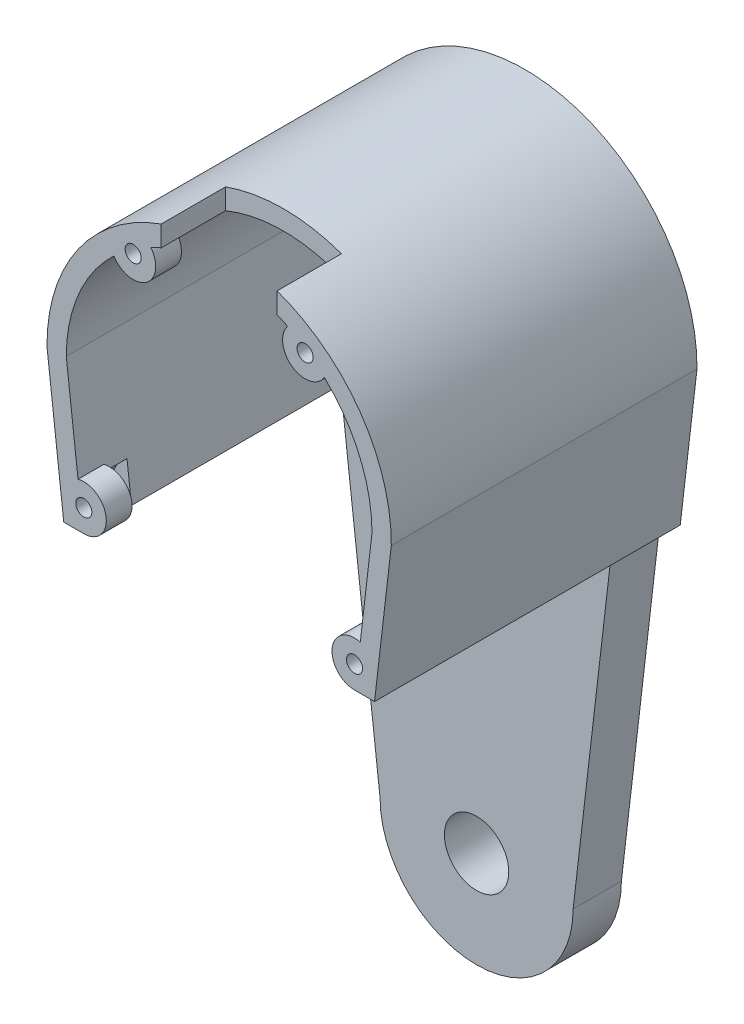
SolidWorks part; units mm, degrees
material "PLA"
ref_plane "Front" through (0, 0, 0) normal (0, 0, 1) x (1, 0, 0)
ref_plane "Top" through (0, 0, 0) normal (0, 1, 0) x (1, 0, 0)
ref_plane "Right" through (0, 0, 0) normal (1, 0, 0) x (0, 0, -1)
other "Configuration Table"
sketch "Esquisse1" plane through (0, 0, 0) normal (0, 0, 1) x (1, 0, 0)
  line L0 (23.75, 0) -> (15, -75)
  line L1 (-23.75, 0) -> (-15, -75)
  line L3 (5, 5) -> (-5, 5)
  line L4 (5, 5) -> (5, -5)
  line L5 (5, -5) -> (-5, -5)
  line L6 (-5, 5) -> (-5, -5)
  line L7 (5, 5) -> (-5, -5) construction
  line L8 (5, -5) -> (-5, 5) construction
  circle A0 centre (0, 0) radius 23.75
  circle A1 centre (0, -75) radius 15
  circle A2 centre (5, 5) radius 1.25
  circle A3 centre (-5, 5) radius 1.25
  circle A4 centre (-5, -5) radius 1.25
  circle A5 centre (5, -5) radius 1.25
  circle A6 centre (0, -75) radius 5
  dimension "D1" = 47.5
  dimension "D2" = 30
  dimension "D5" = 2.5
  dimension "D6" = 10
  dimension "D3" = 75
  dimension "D4" = 10
extrude "Boss.-Extru.1" add sketch "Esquisse1" along normal blind 7.5 contours A1 A6 | A1 L0 A0 L1 | L0 A0 L1 A5 L5 A4 L6 A3 L3 A2 L4 | A5 L4 A2 L3 A3 L6 A4 L5 region at (22.7639, -2.6558, 0) region at (0, -40.5261, 0) region at (0, -89.5757, 0) region at (0, 0, 0)
sketch "Esquisse2" plane through (0, 0, 7.5) normal (0, 0, 1) x (1, 0, 0)
  line L0 (23.75, 0) -> (15, -75) construction
  line L1 (-23.75, 0) -> (-15, -75) construction
  line L2 (23.75, 0) -> (15, -75)
  line L3 (-23.75, 0) -> (-15, -75)
  line L4 (26.7494, -0.1796) -> (17.9798, -75.3476)
  line L5 (-26.7494, -0.1796) -> (-17.9798, -75.3476)
  line L6 (-24.1453, -22.5) -> (24.1453, -22.5)
  arc A0 (23.75, 0) -> (-23.75, 0) centre (0, 0) ccw construction
  arc A1 (23.75, 0) -> (-23.75, 0) centre (0, 0) ccw
  arc A2 (26.7494, -0.1796) -> (-26.7494, -0.1796) centre (0, 0) ccw
  arc M10 (23.75, 0) -> (-23.75, 0) centre (0, 0) ccw
  line M11 (-23.75, 0) -> (-15, -75)
  dimension "D2" = 22.5
  dimension "D1" = 3
extrude "Boss.-Extru.2" add sketch "Esquisse2" along normal blind 40 and the other way up to surface (7.5 mm away) contours L4 A2 L5 L6 L2 M11 M10 | L4 | L5 | A2 | A2 region at (0, 24.4772, 7.5) other way up to face at (-3.75, -5, 0)
sketch "Esquisse4" plane through (0, 0, 47.5) normal (0, 0, 1) x (1, 0, 0)
  line L1 (-9, 33.0526) -> (9, 33.0526)
  line L2 (-9, 33.0526) -> (-9, 20.4474)
  line L3 (-9, 20.4474) -> (9, 20.4474)
  line L4 (9, 33.0526) -> (9, 20.4474)
  line L5 (-9, 33.0526) -> (9, 20.4474) construction
  line L6 (-9, 20.4474) -> (9, 33.0526) construction
  arc A0 (26.7494, -0.1796) -> (-26.7494, -0.1796) centre (0, 0) ccw construction
  point P0 (0, 26.75)
  dimension "D1" = 18
extrude "Enlèv. mat.-Extru.1" cut sketch "Esquisse4" against normal blind 10
sketch "Esquisse5" plane through (0, 0, 47.5) normal (0, 0, 1) x (1, 0, 0)
  line L6 (-26.7494, -0.1796) -> (-24.1453, -22.5) construction
  arc A1 (-9, 25.1905) -> (-26.7494, -0.1796) centre (0, 0) ccw construction
  line B0 (-11.6401, 21.3541) -> (-14.5086, 21.678)
  line B1 (-14.5086, 21.678) -> (-16.2234, 19.3558)
  line B2 (-16.2234, 19.3558) -> (-15.0696, 16.7096)
  line B3 (-15.0696, 16.7096) -> (-12.2011, 16.3857)
  line B4 (-12.2011, 16.3857) -> (-10.4863, 18.7079)
  line B5 (-10.4863, 18.7079) -> (-11.6401, 21.3541)
  circle B6 centre (-13.3548, 19.0318) radius 2.5 construction
  circle B7 centre (-13.3548, 19.0318) radius 3.5
  circle B8 centre (-13.3548, 19.0318) radius 1.25
  line B9 (-19.7052, -16.4364) -> (-22.5887, -16.5717)
  line B10 (-22.5887, -16.5717) -> (-23.9134, -19.1366)
  line B11 (-23.9134, -19.1366) -> (-22.3544, -21.5662)
  line B12 (-22.3544, -21.5662) -> (-19.4708, -21.4309)
  line B13 (-19.4708, -21.4309) -> (-18.1462, -18.866)
  line B14 (-18.1462, -18.866) -> (-19.7052, -16.4364)
  circle B15 centre (-21.0298, -19.0013) radius 2.5 construction
  circle B16 centre (-21.0298, -19.0013) radius 3.5
  circle B17 centre (-21.0298, -19.0013) radius 1.25
  line M14 (-21.125, -22.5) -> (-23.75, 0)
  arc M15 (-23.75, 0) -> (-9, 21.9787) centre (0, 0) cw
sketch_block_instance "Bloc1-1"
sketch_block "Bloc1" parameters "D1"=5, "D2"=7, "D3"=2.5
sketch_block_instance "Bloc1-2"
extrude "Enlèv. mat.-Extru.2" cut sketch "Esquisse5" against normal blind 7.5 contours B8 B5 B0 B1 B2 M15 | B8 B2 B3 B4 B5 M15 | B8 M15 | B8 M15 | B17 B9 B10 B11 B12 M14 | B17 B12 B13 B14 B9 M14 | B17 region at (-14.1665, 20.2449, 47.5) region at (-11.0108, 19.7414, 47.5) region at (-13.8166, 19.6899, 47.5) region at (-13.1954, 18.8046, 47.5) region at (-22.5067, -19.1629, 47.5) region at (-20.7601, -16.5486, 47.5)
extrude "Boss.-Extru.3" add sketch "Esquisse5<3>" against normal blind 4 contours B7 B5 B4 B3 B2 M15 | B16 B9 B14 B13 B12 M14 region at (-10.9851, 20.9592, 47.5) region at (-18.9463, -16.2925, 47.5)
sketch "Esquisse5<3>" plane through (0, 0, 47.5) normal (0, 0, 1) x (1, 0, 0) same geometry as "Esquisse5"
extrude "Boss.-Extru.4" add sketch "Esquisse5<4>" against normal blind 2 contours B8 B5 B0 B1 B2 M15 | B8 B2 B3 B4 B5 M15 | B17 B12 B13 B14 B9 M14 | B17 B9 B10 B11 B12 M14 region at (-14.1665, 20.2449, 47.5) region at (-11.0108, 19.7414, 47.5) region at (-22.5067, -19.1629, 47.5) region at (-20.7601, -16.5486, 47.5)
sketch "Esquisse5<4>" plane through (0, 0, 47.5) normal (0, 0, 1) x (1, 0, 0) same geometry as "Esquisse5"
mirror "Symétrie1" about plane through (0, 0, 0) normal (1, 0, 0) of "Enlèv. mat.-Extru.2", "Boss.-Extru.3", "Boss.-Extru.4"
sketch "Esquisse6" plane through (0, 0, 7.5) normal (0, 0, 1) x (1, 0, 0)
  circle A0 centre (0, 0) radius 1.5
  dimension "D1" = 3
extrude "Enlèv. mat.-Extru.3" cut sketch "Esquisse6" against normal blind 10
sketch "Esquisse7" plane through (0, 0, 7.5) normal (0, 0, 1) x (1, 0, 0)
  circle A0 centre (0, 0) radius 3.1
  dimension "D1" = 6.2
extrude "Enlèv. mat.-Extru.4" cut sketch "Esquisse7" against normal blind 2.5
sketch "Esquisse8" plane through (0, 0, 7.5) normal (0, 0, 1) x (1, 0, 0)
  circle A0 centre (0, 0) radius 3.6
  dimension "D1" = 7.2
extrude "Enlèv. mat.-Extru.5" cut sketch "Esquisse8" against normal blind 0.7
